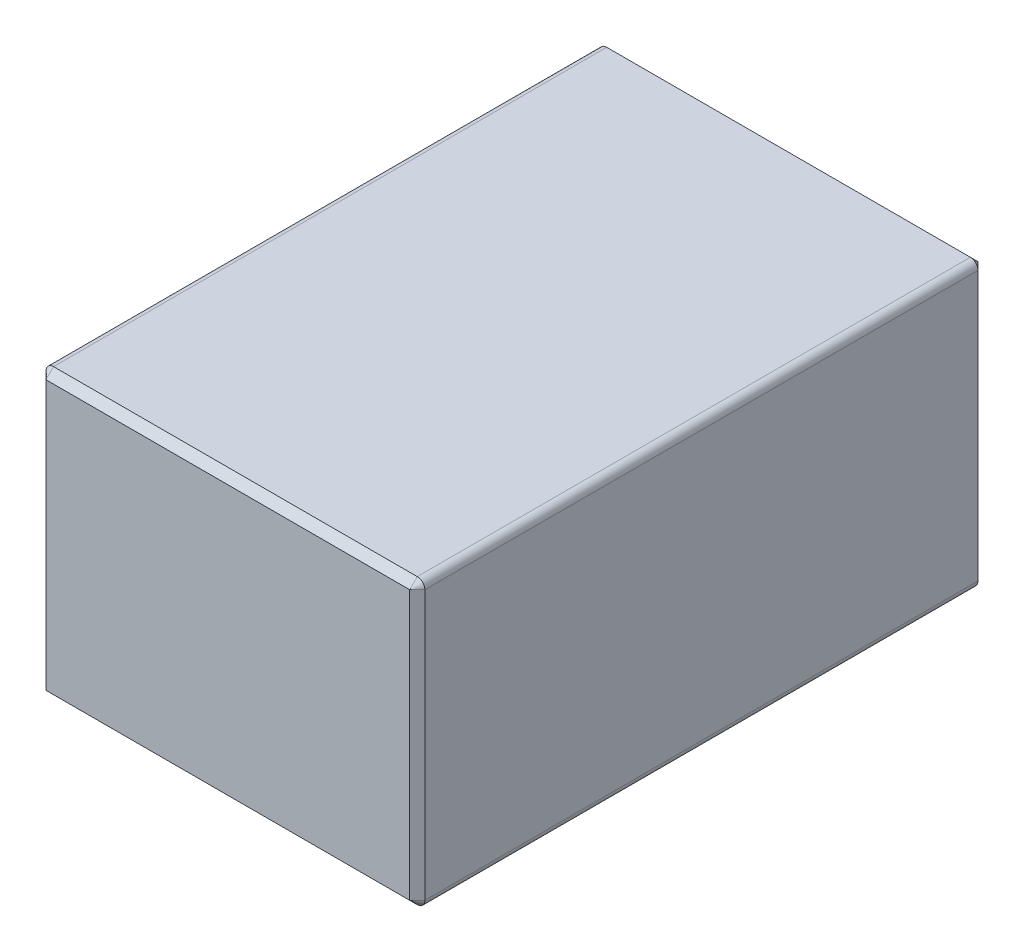
SolidWorks part; units mm, degrees
ref_plane "Front Plane" through (0, 0, 0) normal (0, 0, 1) x (1, 0, 0)
ref_plane "Top Plane" through (0, 0, 0) normal (0, 1, 0) x (1, 0, 0)
ref_plane "Right Plane" through (0, 0, 0) normal (1, 0, 0) x (0, 0, -1)
sketch "Sketch1" plane through (0, 0, 0) normal (0, 1, 0) x (1, 0, 0)
  line L1 (-50, 75) -> (50, 75)
  line L2 (-50, 75) -> (-50, -75)
  line L3 (-50, -75) -> (50, -75)
  line L4 (50, 75) -> (50, -75)
  line L5 (-50, 75) -> (50, -75) construction
  line L6 (-50, -75) -> (50, 75) construction
  point P0 (0, 0)
  dimension "D1" = 100
  dimension "D2" = 150
extrude "Boss-Extrude1" add sketch "Sketch1" along normal blind 75
fillet "Fillet1" radius 2 4 edges at (-50, 0, 0) (50, 0, 0) (-50, 75, 0) (50, 75, 0)
chamfer "Chamfer1" distance 2 angle 45 16 edges at (49.4142, 0.5858, -75) (50, 37.5, -75) (49.4142, 74.4142, -75) (0, 75, -75) (-49.4142, 74.4142, -75) (-50, 37.5, -75) (-49.4142, 0.5858, -75) (0, 0, -75) (-49.4142, 74.4142, 75) (0, 75, 75) (49.4142, 74.4142, 75) (50, 37.5, 75) (49.4142, 0.5858, 75) (0, 0, 75) (-49.4142, 0.5858, 75) (-50, 37.5, 75)
